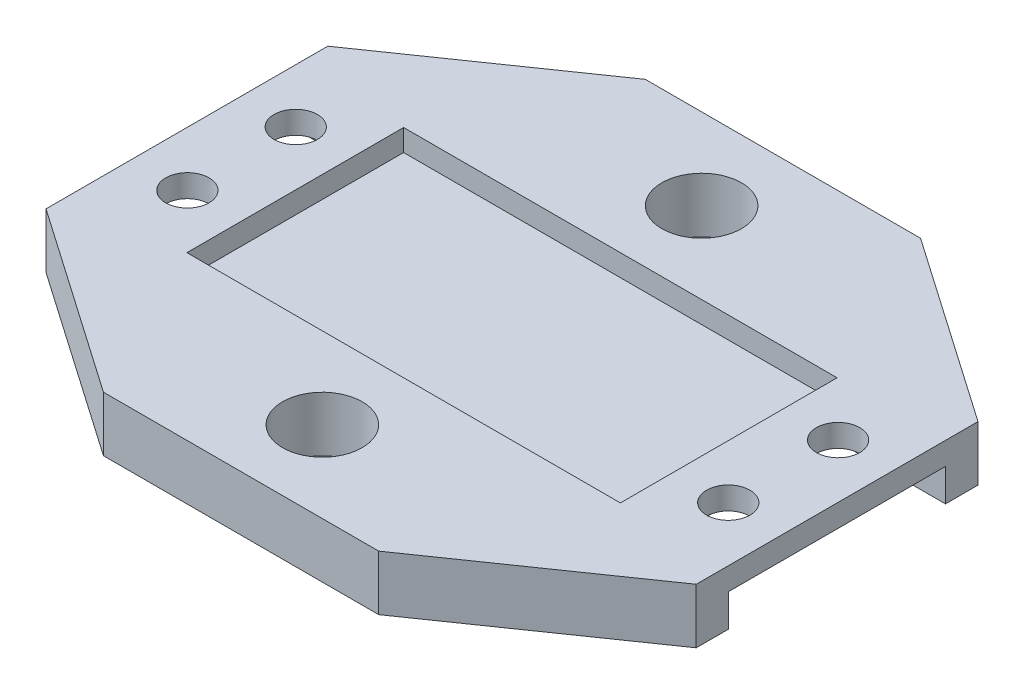
SolidWorks part; units mm, degrees
ref_plane "Front Plane" through (0, 0, 0) normal (0, 0, 1) x (1, 0, 0)
ref_plane "Top Plane" through (0, 0, 0) normal (0, 1, 0) x (1, 0, 0)
ref_plane "Right Plane" through (0, 0, 0) normal (1, 0, 0) x (0, 0, -1)
sketch "Sketch1" plane through (0, 0, 0) normal (0, 1, 0) x (1, 0, 0)
  line L0 (-48.0587, 12.2268) -> (11.9413, 12.2268) construction
  line L1 (-48.0587, 27.2268) -> (11.9413, 27.2268)
  line L2 (-48.0587, 27.2268) -> (-48.0587, -22.7732)
  line L3 (-48.0587, -22.7732) -> (11.9413, -22.7732)
  line L4 (11.9413, 27.2268) -> (11.9413, -22.7732)
  line L5 (11.9413, -7.7732) -> (-48.0587, -7.7732) construction
  line L6 (-18.0587, 27.2268) -> (-18.0587, -22.7732) construction
  dimension "D1" = 60
  dimension "D2" = 50
  dimension "D3" = 15
  dimension "D4" = 15
extrude "Boss-Extrude1" add sketch "Sketch1" along normal blind 5.08
sketch "Sketch2" plane through (0, 5.08, 0) normal (0, 1, 0) x (1, 0, 0)
  line L0 (-18.0587, 27.2268) -> (-18.0587, -22.7732) construction
  line L1 (11.9413, 27.2268) -> (-48.0587, 27.2268) construction
  line L2 (-48.0587, -22.7732) -> (11.9413, -22.7732) construction
  line L3 (-30.7587, 27.2268) -> (-5.3587, 27.2268)
  line L4 (-30.7587, 27.2268) -> (-48.0587, 15.2268)
  line L5 (-48.0587, 27.2268) -> (-48.0587, -22.7732) construction
  line L6 (-5.3587, 27.2268) -> (11.9413, 15.2268)
  line L7 (11.9413, -22.7732) -> (11.9413, 27.2268) construction
  line L8 (11.9413, 2.2268) -> (-48.0587, 2.2268) construction
  line L9 (-30.7587, -22.7732) -> (-48.0587, -10.7732)
  line L10 (-30.7587, -22.7732) -> (-5.3587, -22.7732)
  line L11 (-5.3587, -22.7732) -> (11.9413, -10.7732)
  line L12 (-48.0587, 15.2268) -> (-48.0587, -10.7732)
  line L13 (11.9413, -10.7732) -> (11.9413, 15.2268)
  circle A0 centre (-18.0587, 19.7268) radius 3.675
  circle A1 centre (-18.0587, -15.2732) radius 3.675
  dimension "D4" = 7.5
  dimension "D5" = 7.35
  dimension "D1" = 25.4
  dimension "D2" = 12
  dimension "D3" = 12
extrude "Cut-Extrude1" cut sketch "Sketch2" against normal through all flip side to cut
sketch "Sketch12" plane through (-48.0587, 0, 0) normal (-1, 0, 0) x (0, 0, 1)
  line L0 (-15.2268, 0) -> (10.7732, 0) construction
  line L1 (7.815, 0) -> (-12.185, 0)
  line L2 (7.815, 0) -> (7.815, 3)
  line L3 (7.815, 3) -> (-12.185, 3)
  line L4 (-12.185, 0) -> (-12.185, 3)
  dimension "D1" = 20
  dimension "D2" = 3
extrude "Cut-Extrude6" cut sketch "Sketch12" against normal blind 10
sketch "Sketch13" plane through (11.9413, 0, 0) normal (1, 0, 0) x (0, 0, -1)
  line L0 (-10.7732, 0) -> (15.2268, 0) construction
  line L1 (12.2268, 0) -> (-7.7732, 0)
  line L2 (12.2268, 0) -> (12.2268, 3)
  line L3 (12.2268, 3) -> (-7.7732, 3)
  line L4 (-7.7732, 0) -> (-7.7732, 3)
  dimension "D1" = 3
  dimension "D2" = 20
  dimension "D3" = 3
extrude "Cut-Extrude7" cut sketch "Sketch13" against normal blind 10
sketch "Sketch14" plane through (0, 5.08, 0) normal (0, 1, 0) x (1, 0, 0)
  line L0 (-18.0587, 27.2268) -> (-18.0587, -22.7732) construction
  line L1 (-5.3587, 27.2268) -> (-30.7587, 27.2268) construction
  line L2 (-30.7587, -22.7732) -> (-5.3587, -22.7732) construction
  line L4 (-38.0587, -7.7732) -> (1.9413, -7.7732)
  line L5 (-38.0587, -7.7732) -> (-38.0587, 12.2268)
  line L6 (-38.0587, 12.2268) -> (1.9413, 12.2268)
  line L7 (1.9413, -7.7732) -> (1.9413, 12.2268)
  line L8 (-38.0587, -7.7732) -> (1.9413, 12.2268) construction
  line L9 (-38.0587, 12.2268) -> (1.9413, -7.7732) construction
  point P6 (-18.0587, 2.2268)
  dimension "D1" = 40
  dimension "D2" = 20
extrude "Cut-Extrude8" cut sketch "Sketch14" against normal blind 2
sketch "Sketch15" plane through (0, 5.08, 0) normal (0, 1, 0) x (1, 0, 0)
  line L0 (11.9413, 2.6225) -> (-48.0587, 2.2268) construction
  line L1 (11.9413, -10.7732) -> (11.9413, 15.2268) construction
  line L2 (-48.0587, 15.2268) -> (-48.0587, -10.7732) construction
  line L3 (-18.0587, 27.2268) -> (-18.0587, -22.7732) construction
  line L4 (-5.3587, 27.2268) -> (-30.7587, 27.2268) construction
  line L5 (-30.7587, -22.7732) -> (-5.3587, -22.7732) construction
  circle A0 centre (-43.0152, -2.7732) radius 2
  circle A1 centre (-43.0816, 7.2929) radius 2
  circle A2 centre (6.9642, 7.2929) radius 2
  circle A3 centre (6.8978, -2.7732) radius 2
  dimension "D1" = 4
  dimension "D2" = 5
extrude "Cut-Extrude9" cut sketch "Sketch15" against normal through all
